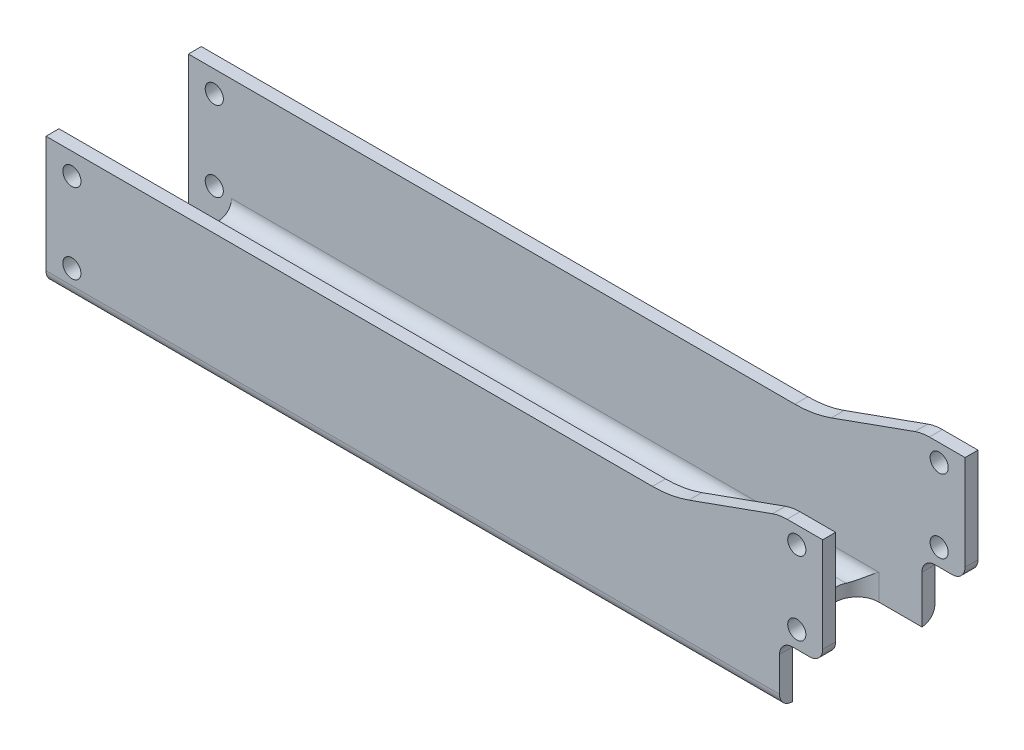
SolidWorks part; units mm, degrees
ref_plane "Front Plane" through (0, 0, 0) normal (0, 0, 1) x (1, 0, 0)
ref_plane "Top Plane" through (0, 0, 0) normal (0, 1, 0) x (1, 0, 0)
ref_plane "Right Plane" through (0, 0, 0) normal (1, 0, 0) x (0, 0, -1)
sketch "Sketch1" plane through (0, 0, 0) normal (0, 0, 1) x (1, 0, 0)
  line L0 (52.7874, 245.1803) -> (193.3525, 245.1803)
  line L4 (52.7874, 245.1803) -> (52.7874, 215.1803)
  line L5 (52.7874, 215.1803) -> (222.7874, 215.1803)
  line L6 (222.7874, 245.1803) -> (222.7874, 215.1803) construction
  line L7 (222.7874, 215.1803) -> (222.7874, 254.1811)
  line L8 (222.7874, 254.1811) -> (201.7956, 246.6492)
  line L9 (241.0832, 254.1811) -> (222.7874, 254.1811) construction
  arc A0 (201.7956, 246.6492) -> (193.3525, 245.1803) centre (193.3525, 270.1803) cw
extrude "Boss-Extrude1" add sketch "Sketch1" against normal blind 3
sketch "Sketch3" plane through (0, 0, -36) normal (0, 0, -1) x (-1, 0, 0)
  line L4 (-222.7874, 254.1811) -> (-222.7874, 215.1803)
  line L5 (-222.7874, 254.1811) -> (-222.7874, 215.1803)
  line L6 (-52.7874, 215.1803) -> (-52.7874, 245.1803)
  line L7 (-52.7874, 245.1803) -> (-193.3525, 245.1803)
  line L9 (-201.7956, 246.6492) -> (-222.7874, 254.1811)
  line L10 (-201.7956, 246.6492) -> (-222.7874, 254.1811)
  line L11 (-222.7874, 215.1803) -> (-52.7874, 215.1803)
  line L12 (-52.7874, 215.1803) -> (-52.7874, 245.1803)
  line L13 (-52.7874, 245.1803) -> (-193.3525, 245.1803)
  line L17 (-222.7874, 215.1803) -> (-52.7874, 215.1803)
  arc A1 (-201.7956, 246.6492) -> (-193.3525, 245.1803) centre (-193.3525, 270.1803) ccw
  arc A2 (-201.7956, 246.6492) -> (-193.3525, 245.1803) centre (-193.3525, 270.1803) ccw
  dimension "D1" = 0
extrude "Boss-Extrude2" add sketch "Sketch3" against normal blind 3 separate body
sketch "Sketch4" plane through (0, 0, -3) normal (0, 0, -1) x (-1, 0, 0)
  line L1 (-52.7874, 215.1803) -> (-207.7874, 215.1803)
  line L2 (-52.7874, 215.1803) -> (-52.7874, 218.1803)
  line L3 (-52.7874, 218.1803) -> (-207.7874, 218.1803)
  line L4 (-207.7874, 215.1803) -> (-207.7874, 218.1803)
extrude "Boss-Extrude3" add sketch "Sketch4" along normal up to surface (30 mm away) up to face at (157.7268, 236.8645, -33)
fillet "Fillet1" radius 5 2 edges at (207.7874, 216.6803, -33) (207.7874, 216.6803, -3)
ref_plane "Plane1" through (130.2874, 0, 0) normal (1, 0, 0) x (0, 0, -1)
fillet "Fillet2" radius 3 4 edges at (132.7874, 218.1803, -3) (132.7874, 218.1803, -33) (137.7874, 215.1803, 0) (137.7874, 215.1803, -36)
sketch "Sketch5" plane through (0, 218.1803, 0) normal (0, 1, 0) x (1, 0, 0)
  line L0 (52.7874, 33) -> (193.3525, 33) construction
  line L1 (52.7874, 3) -> (62.7874, 3)
  line L2 (52.7874, 3) -> (52.7874, 33)
  line L3 (52.7874, 33) -> (62.7874, 33)
  line L4 (62.7874, 3) -> (62.7874, 33)
extrude "Cut-Extrude1" cut sketch "Sketch5" against normal through all both and the other way through all
sketch "Sketch6" plane through (0, 0, 0) normal (0, 0, 1) x (1, 0, 0)
  line L4 (54.7876, 245.1805) -> (62.7877, 245.1806) construction
  line L5 (58.7876, 245.1805) -> (58.7876, 215.1803) construction
  line L6 (52.7874, 215.1803) -> (62.7874, 215.1803) construction
  circle A0 centre (58.7876, 240.1805) radius 2.1
  circle A1 centre (58.7876, 221.6803) radius 2.1
extrude "Cut-Extrude2" cut sketch "Sketch6" against normal up to surface (36 mm away) up to face at (157.7268, 237.8645, -36)
sketch "Sketch7" plane through (222.7874, 0, 0) normal (1, 0, 0) x (0, 0, -1)
  line L0 (0, 218.1803) -> (0, 254.1811) construction
  line L1 (3, 254.1811) -> (0, 254.1811)
  line L2 (3, 254.1811) -> (3, 229.1811)
  line L3 (3, 229.1811) -> (0, 229.1811)
  line L4 (0, 254.1811) -> (0, 229.1811)
  line L5 (36, 254.1811) -> (36, 218.1803) construction
  line L6 (33, 254.1811) -> (36, 254.1811)
  line L7 (33, 254.1811) -> (33, 229.1811)
  line L8 (33, 229.1811) -> (36, 229.1811)
  line L9 (36, 254.1811) -> (36, 229.1811)
extrude "Boss-Extrude4" add sketch "Sketch7" along normal blind 10
fillet "Fillet3" radius 3 4 edges at (222.7874, 229.1811, -34.5) (222.7874, 229.1811, -1.5) (232.7874, 229.1811, -34.5) (232.7874, 229.1811, -1.5)
sketch "Sketch9" plane through (0, 0, 0) normal (0, 0, 1) x (1, 0, 0)
  line L4 (222.7874, 254.1811) -> (230.7874, 254.1811) construction
  line L5 (226.7874, 254.1811) -> (226.7874, 229.1811) construction
  circle A0 centre (226.7874, 250.1811) radius 2.1
  circle A1 centre (226.7874, 233.1811) radius 2.1
extrude "Cut-Extrude3" cut sketch "Sketch9" against normal up to surface (36 mm away) up to face at (58.7876, 242.2805, -36)
fillet "Fillet4" radius 10 2 edges at (222.7874, 254.1811, -34.5) (222.7874, 254.1811, -1.5)
